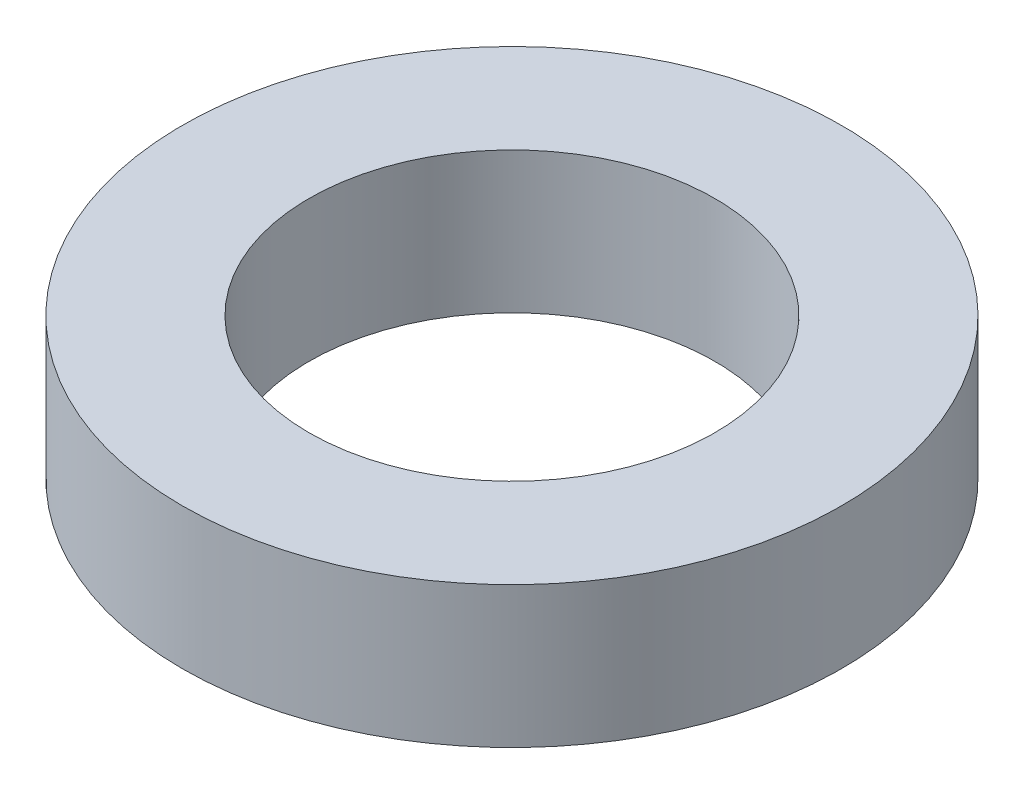
SolidWorks part; units mm, degrees
ref_plane "Front Plane" through (0, 0, 0) normal (0, 0, 1) x (1, 0, 0)
ref_plane "Top Plane" through (0, 0, 0) normal (0, 1, 0) x (1, 0, 0)
ref_plane "Right Plane" through (0, 0, 0) normal (1, 0, 0) x (0, 0, -1)
sketch "Sketch1" plane through (0, 0, 0) normal (0, 1, 0) x (1, 0, 0)
  circle A0 centre (0, 0) radius 23.7
  circle A1 centre (0, 0) radius 25.25
  circle A2 centre (0, 0) radius 30.3694
  circle A3 centre (0, 0) radius 18.7
  dimension "D1" = 47.4
  dimension "D2" = 50.5
  dimension "D4" = 60.7388
  dimension "D3" = 5
extrude "Boss-Extrude1" add sketch "Sketch1" against normal blind 10 contours A2 A1 | A0 A3 region at (-23.0297, 0, 0) region at (-29.5104, 0, 0)
sketch "Sketch2" plane through (0, 0, 0) normal (0, 1, 0) x (1, 0, 0)
  circle A0 centre (0, 0) radius 30.3694
  circle A1 centre (0, 0) radius 18.7
  dimension "D1" = 60.7388
  dimension "D2" = 37.4
extrude "Boss-Extrude2" add sketch "Sketch2" along normal blind 3
sketch "Sketch3" plane through (0, 3, 0) normal (0, 1, 0) x (1, 0, 0)
  line L1 (29.7827, -5.9407) -> (-29.7827, -5.9407)
  line L2 (29.7827, -5.9407) -> (29.7827, 5.9407)
  line L3 (29.7827, 5.9407) -> (-29.7827, 5.9407)
  line L4 (-29.7827, -5.9407) -> (-29.7827, 5.9407)
  line L5 (29.7827, -5.9407) -> (-29.7827, 5.9407) construction
  line L6 (29.7827, 5.9407) -> (-29.7827, -5.9407) construction
  circle A0 centre (0, 0) radius 30.3694
  point P0 (0, 0)
  dimension "D3" = 60.7388
  dimension "D1" = 11.8814
  dimension "D2" = 59.5654
equation "\"tubeInnerDiameter\"= 47.4"
equation "\"D1@Sketch1\"=\"tubeInnerDiameter\""
equation "\"tubeOuterDiameter\"= 50.5"
equation "\"D2@Sketch1\"=\"tubeOuterDiameter\""
equation "\"noseOuterDiameter\" = ( ( ( \"phoneThickness\" / 2 ) ^ 2 + ( \"phoneWidth\" / 2 ) ^ 2 ) ^ 0.5 ) * 2"
equation "\"D4@Sketch1\"=\"noseOuterDiameter\""
equation "\"tubeMountingHeight\"=10"
equation "\"D1@Boss-Extrude1\"=\"tubeMountingHeight\""
equation "\"phoneWidth\"=59.5654"
equation "\"phoneThickness\"=11.8814"
equation "\"D1@Sketch2\"=\"noseOuterDiameter\""
equation "\"D2@Sketch2\"=\"tubeInnerDiameter\"-10"
equation "\"D1@Sketch3\"=\"phoneThickness\""
equation "\"D2@Sketch3\"=\"phoneWidth\""
equation "\"D3@Sketch3\"=\"noseOuterDiameter\""
